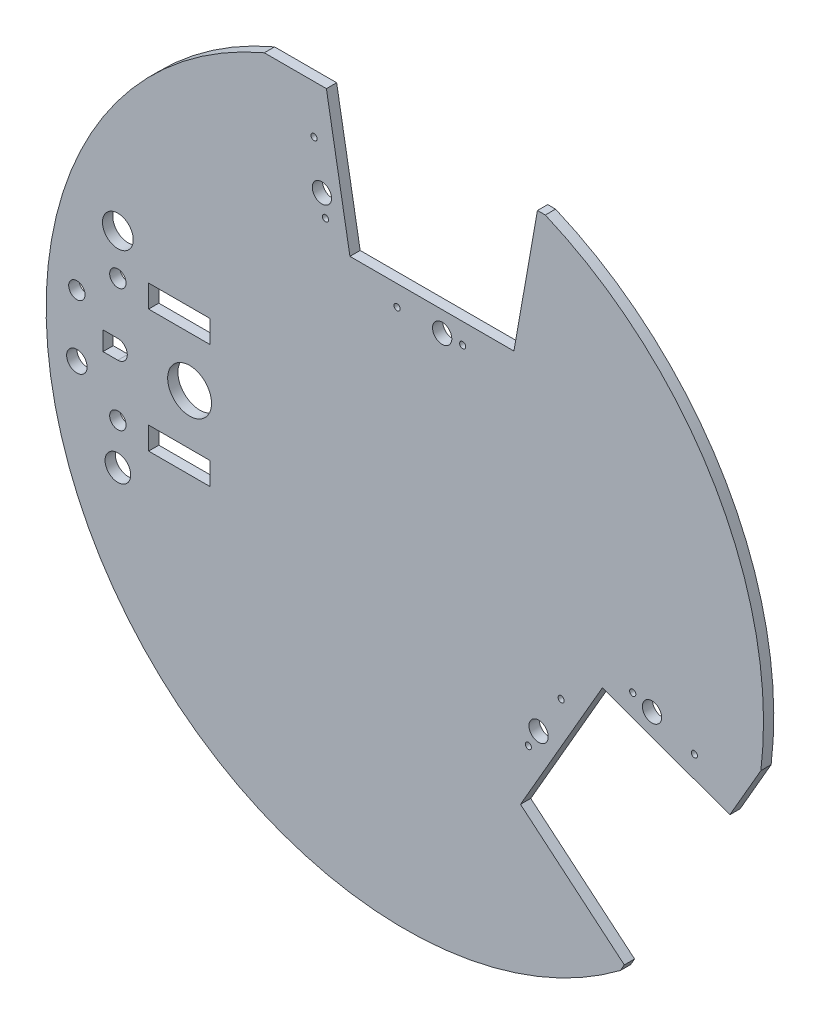
SolidWorks part; units mm, degrees
material "Balsa"
ref_plane "Plan de face" through (0, 0, 0) normal (0, 0, 1) x (1, 0, 0)
ref_plane "Plan de dessus" through (0, 0, 0) normal (0, 1, 0) x (1, 0, 0)
ref_plane "Plan de droite" through (0, 0, 0) normal (1, 0, 0) x (0, 0, -1)
sketch "Esquisse1" plane through (0, 0, 0) normal (0, 0, 1) x (1, 0, 0)
  circle A0 centre (0, 0) radius 175
extrude "Boss.-Extru.1" add sketch "Esquisse1" along normal blind 5
sketch "Esquisse2" plane through (0, 0, 0) normal (0, 0, -1) x (-1, 0, 0)
  line L1 (-13.2204, 90.8876) -> (-13.2204, 0) construction
  line L3 (0, 0) -> (-290.6498, 0) construction
  line L5 (26.7796, 95.8876) -> (38.2633, 161.0152)
  line L6 (38.2633, 161.0152) -> (68.5501, 161.0152)
  line L7 (68.5501, 161.0152) -> (68.5501, 190.2461)
  line L8 (-53.2204, 95.8876) -> (-64.7042, 161.0152)
  line L9 (-64.7042, 161.0152) -> (-94.991, 161.0152)
  line L10 (-94.991, 161.0152) -> (-94.991, 190.2461)
  line L11 (-94.991, 190.2461) -> (68.5501, 190.2461)
  line L12 (26.7796, 95.8876) -> (-53.2204, 95.8876)
  line L13 (-96.4309, -24.752) -> (-158.5749, -47.3706)
  line L14 (-158.5749, -47.3706) -> (-173.7183, -21.1414)
  line L15 (-173.7183, -21.1414) -> (-199.033, -35.7569)
  line L16 (-56.4309, -94.034) -> (-107.0911, -136.543)
  line L17 (-107.0911, -136.543) -> (-91.9477, -162.7722)
  line L18 (-91.9477, -162.7722) -> (-117.2625, -177.3877)
  line L19 (-117.2625, -177.3877) -> (-199.033, -35.7569)
  line L20 (-96.4309, -24.752) -> (-56.4309, -94.034)
  line L21 (-72.1008, -56.893) -> (6.6102, -11.4492) construction
  line L22 (0, 0) -> (87.5, -151.5544) construction
  circle A0 centre (-18.2204, 85.8876) radius 4.7
  circle A1 centre (40.4604, 115.8876) radius 4.7
  circle A2 centre (-65.2706, -58.7232) radius 4.7
  circle A3 centre (-120.5918, -22.9041) radius 4.7
  circle A4 centre (0, 0) radius 175 construction
  point P43 (0, 0)
  dimension "D5" = 9.4
  dimension "D6" = 9.4
  dimension "D1" = 2
  dimension "D2" = 95.8876
  dimension "D3" = 13.2204
  dimension "D4" = 100
  dimension "D7" = 80
  dimension "D8" = 65.1275
extrude "Enlèv. mat.-Extru.1" cut sketch "Esquisse2" against normal blind 5
sketch "Leds, bout., tirette" plane through (0, 0, 5) normal (0, 0, 1) x (1, 0, 0)
  line L0 (0, 0) -> (0, 203.1142) construction
  line L1 (0, 0) -> (-214.6297, 0) construction
  line L2 (-156.4682, 78.3754) -> (-90, 40) construction
  line L3 (-90, 40) -> (-90, -40) construction
  line L4 (-90, -40) -> (-156.4682, -78.3754) construction
  line L5 (-140, 0) -> (-89.4612, 0) construction
  line L6 (-140, -4.6) -> (-147.25, -4.6)
  line L7 (-140, 4.6) -> (-147.25, 4.6)
  line L8 (-147.25, 4.6) -> (-147.25, -4.6)
  line L9 (-125, 35.5) -> (-95, 35.5)
  line L10 (-125, 35.5) -> (-125, 24.5)
  line L11 (-95, 35.5) -> (-95, 24.5)
  line L12 (-125, 24.5) -> (-95, 24.5)
  line L13 (-125, -24.5) -> (-95, -24.5)
  line L14 (-125, -24.5) -> (-125, -35.5)
  line L15 (-95, -24.5) -> (-95, -35.5)
  line L16 (-125, -35.5) -> (-95, -35.5)
  line L17 (-95, -30) -> (-140, -30) construction
  line L18 (-95, 30) -> (-140, 30) construction
  line L19 (-140, 4.6) -> (-140, -4.6) construction
  arc A0 (-68.5501, 161.0152) -> (105.1682, -139.8737) centre (0, 0) ccw construction
  arc A1 (-156.4682, 78.3754) -> (-156.4682, -78.3754) centre (0, 0) ccw construction
  circle A2 centre (-105, 0) radius 10.7
  circle A3 centre (-140, -50) radius 6.25
  circle A4 centre (-140, 30) radius 4
  circle A5 centre (-140, -30) radius 4
  circle A6 centre (-160, 15) radius 4
  circle A7 centre (-160, -15) radius 5
  arc A8 (-140, -4.6) -> (-140, 4.6) centre (-140, 0) ccw
  circle A9 centre (-140, 50) radius 7.5
  point P26 (-13.0506, -157.1537)
  dimension "D2" = 90
  dimension "D5" = 12.5
  dimension "D6" = 21.4
  dimension "D7" = 8
  dimension "D8" = 10
  dimension "D9" = 4.6
  dimension "D12" = 15
  dimension "D1" = 90
  dimension "D3" = 80
  dimension "D4" = 120
  dimension "D10" = 9.2
  dimension "D11" = 7.25
  dimension "D13" = 11
  dimension "D14" = 30
  dimension "D15" = 5
  dimension "D16" = 30
  dimension "D17" = 45
  dimension "D18" = 15
  dimension "D19" = 35
  dimension "D20" = 70
  dimension "D21" = 15
  dimension "D22" = 50
  dimension "D23" = 50
extrude "Leds, buttons" cut sketch "Leds, bout., tirette" against normal blind 10
sketch "Fixation acensseurs" plane through (0, 0, 0) normal (0, 0, -1) x (-1, 0, 0)
  line L0 (40.4604, 115.8876) -> (38.7239, 106.0395) construction
  line L1 (26.7796, 95.8876) -> (38.2633, 161.0152) construction
  line L2 (-18.2204, 85.8876) -> (-28.2204, 85.8876) construction
  line L3 (-53.2204, 95.8876) -> (26.7796, 95.8876) construction
  line L4 (-120.5918, -22.9041) -> (-111.1949, -19.4839) construction
  line L5 (-65.2706, -58.7232) -> (-60.2706, -67.3834) construction
  line L6 (-96.4309, -24.752) -> (-158.5749, -47.3706) construction
  line L7 (-56.4309, -94.034) -> (-96.4309, -24.752) construction
  circle A0 centre (38.7239, 106.0395) radius 1.5
  circle A1 centre (-28.2204, 85.8876) radius 1.5
  circle A2 centre (44.2806, 137.5534) radius 1.5
  circle A3 centre (3.7796, 85.8876) radius 1.5
  circle A4 centre (-111.1949, -19.4839) radius 1.5
  circle A5 centre (-60.2706, -67.3834) radius 1.5
  circle A6 centre (-141.265, -30.4285) radius 1.5
  circle A7 centre (-76.2706, -39.6706) radius 1.5
  point P29 (0, 0)
  point P31 (0, 0)
  dimension "D1" = 3
  dimension "D3" = 22
  dimension "D5" = 22
  dimension "D2" = 10
  dimension "D4" = 10
  dimension "D7" = 10
  dimension "D8" = 10
  dimension "D6" = 2
extrude "Enlèv. mat.-Extru.2" cut sketch "Fixation acensseurs" against normal blind 10
